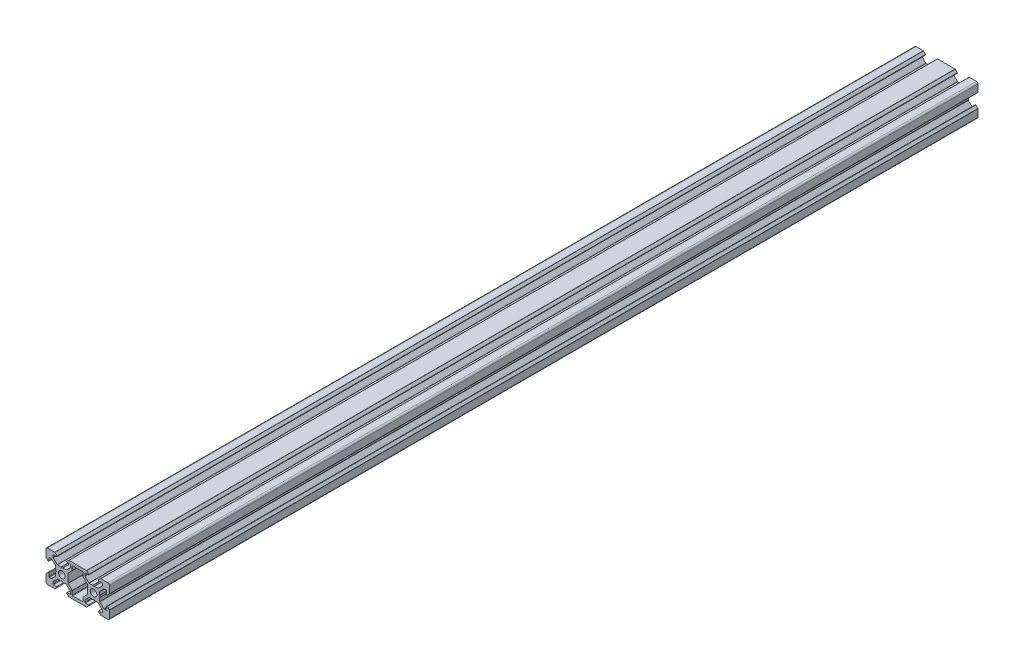
SolidWorks part; units mm, degrees
material "АД31Т ГОСТ 4784-97"
ref_plane "Спереди" through (0, 0, 0) normal (0, 0, 1) x (1, 0, 0)
ref_plane "Сверху" through (0, 0, 0) normal (0, 1, 0) x (1, 0, 0)
ref_plane "Справа" through (0, 0, 0) normal (1, 0, 0) x (0, 0, -1)
sketch "Эскиз1" plane through (0, 0, 0) normal (0, 0, 1) x (1, 0, 0)
  line L0 (12.9654, 0) -> (-12.9654, 0) construction
  line L1 (0, -12.9654) -> (0, 12.9654) construction
  line L2 (0, 0) -> (-18.3359, -18.3359) construction
  line L3 (-10, -10) -> (-10, -4.4)
  line L4 (-10, -4.4) -> (-8.2, -2.6)
  line L5 (-8.2, -2.6) -> (-8.2, -5.4993)
  line L6 (-8.2, -5.4993) -> (-6.56, -5.4993)
  line L7 (-6.56, -5.4993) -> (-3.9007, -2.84)
  line L8 (-3.9007, -2.84) -> (-3.9007, -0.5)
  line L9 (-3.9007, -0.5) -> (-3.4007, 0)
  line L10 (-0.5, -3.9007) -> (0, -3.4007)
  line L11 (-2.84, -3.9007) -> (-0.5, -3.9007)
  line L12 (-5.4993, -6.56) -> (-2.84, -3.9007)
  line L13 (-5.4993, -8.2) -> (-5.4993, -6.56)
  line L14 (-2.6, -8.2) -> (-5.4993, -8.2)
  line L15 (-4.4, -10) -> (-2.6, -8.2)
  line L16 (-10, -10) -> (-4.4, -10)
  line L17 (-10, 10) -> (-4.4, 10)
  line L18 (-4.4, 10) -> (-2.6, 8.2)
  line L19 (-2.6, 8.2) -> (-5.4993, 8.2)
  line L20 (-5.4993, 8.2) -> (-5.4993, 6.56)
  line L21 (-5.4993, 6.56) -> (-2.84, 3.9007)
  line L22 (-2.84, 3.9007) -> (-0.5, 3.9007)
  line L23 (-0.5, 3.9007) -> (0, 3.4007)
  line L24 (-3.9007, 0.5) -> (-3.4007, 0)
  line L25 (-3.9007, 2.84) -> (-3.9007, 0.5)
  line L26 (-6.56, 5.4993) -> (-3.9007, 2.84)
  line L27 (-8.2, 5.4993) -> (-6.56, 5.4993)
  line L28 (-8.2, 2.6) -> (-8.2, 5.4993)
  line L29 (-10, 4.4) -> (-8.2, 2.6)
  line L30 (-10, 10) -> (-10, 4.4)
  line L31 (0.5, 3.9007) -> (0, 3.4007)
  line L32 (0.5, -3.9007) -> (0, -3.4007)
  line L33 (10, -10) -> (10, 10) construction
  line L34 (3.9007, -0.5) -> (3.9007, 0.5)
  line L35 (6.56, -5.4993) -> (6.56, -8.2)
  line L36 (13.44, -5.4993) -> (16.0993, -2.84)
  line L37 (6.56, 5.4993) -> (3.9007, 2.84)
  line L38 (3.9007, 2.84) -> (3.9007, 0.5)
  line L39 (6.56, -8.2) -> (13.44, -8.2)
  line L40 (2.84, 3.9007) -> (0.5, 3.9007)
  line L41 (5.4993, 6.56) -> (2.84, 3.9007)
  line L42 (5.4993, 8.2) -> (5.4993, 6.56)
  line L43 (2.6, 8.2) -> (5.4993, 8.2)
  line L44 (4.4, 10) -> (2.6, 8.2)
  line L45 (15.6, 10) -> (4.4, 10)
  line L46 (15.6, -10) -> (4.4, -10)
  line L47 (4.4, -10) -> (2.6, -8.2)
  line L48 (2.6, -8.2) -> (5.4993, -8.2)
  line L49 (5.4993, -8.2) -> (5.4993, -6.56)
  line L50 (5.4993, -6.56) -> (2.84, -3.9007)
  line L51 (2.84, -3.9007) -> (0.5, -3.9007)
  line L52 (6.56, 5.4993) -> (6.56, 8.2)
  line L53 (3.9007, -2.84) -> (3.9007, -0.5)
  line L54 (6.56, -5.4993) -> (3.9007, -2.84)
  line L55 (16.0993, -2.84) -> (16.0993, -0.5)
  line L56 (6.56, 8.2) -> (13.44, 8.2)
  line L57 (13.44, 5.4993) -> (13.44, 8.2)
  line L58 (17.16, -3.9007) -> (19.5, -3.9007)
  line L59 (14.5007, -6.56) -> (17.16, -3.9007)
  line L60 (14.5007, -8.2) -> (14.5007, -6.56)
  line L61 (17.4, -8.2) -> (14.5007, -8.2)
  line L62 (15.6, -10) -> (17.4, -8.2)
  line L63 (15.6, 10) -> (17.4, 8.2)
  line L64 (17.4, 8.2) -> (14.5007, 8.2)
  line L65 (14.5007, 8.2) -> (14.5007, 6.56)
  line L66 (14.5007, 6.56) -> (17.16, 3.9007)
  line L67 (17.16, 3.9007) -> (19.5, 3.9007)
  line L68 (16.0993, 2.84) -> (16.0993, 0.5)
  line L69 (13.44, 5.4993) -> (16.0993, 2.84)
  line L70 (13.44, -5.4993) -> (13.44, -8.2)
  line L71 (16.0993, -0.5) -> (16.0993, 0.5)
  line L72 (19.5, -3.9007) -> (20, -3.4007)
  line L73 (19.5, 3.9007) -> (20, 3.4007)
  line L74 (30, 10) -> (30, 4.4)
  line L75 (30, 4.4) -> (28.2, 2.6)
  line L76 (28.2, 2.6) -> (28.2, 5.4993)
  line L77 (28.2, 5.4993) -> (26.56, 5.4993)
  line L78 (26.56, 5.4993) -> (23.9007, 2.84)
  line L79 (23.9007, 2.84) -> (23.9007, 0.5)
  line L80 (23.9007, 0.5) -> (23.4007, 0)
  line L81 (20.5, 3.9007) -> (20, 3.4007)
  line L82 (22.84, 3.9007) -> (20.5, 3.9007)
  line L83 (25.4993, 6.56) -> (22.84, 3.9007)
  line L84 (25.4993, 8.2) -> (25.4993, 6.56)
  line L85 (22.6, 8.2) -> (25.4993, 8.2)
  line L86 (24.4, 10) -> (22.6, 8.2)
  line L87 (30, 10) -> (24.4, 10)
  line L88 (30, -10) -> (24.4, -10)
  line L89 (24.4, -10) -> (22.6, -8.2)
  line L90 (22.6, -8.2) -> (25.4993, -8.2)
  line L91 (25.4993, -8.2) -> (25.4993, -6.56)
  line L92 (25.4993, -6.56) -> (22.84, -3.9007)
  line L93 (22.84, -3.9007) -> (20.5, -3.9007)
  line L94 (20.5, -3.9007) -> (20, -3.4007)
  line L95 (23.9007, -0.5) -> (23.4007, 0)
  line L96 (23.9007, -2.84) -> (23.9007, -0.5)
  line L97 (26.56, -5.4993) -> (23.9007, -2.84)
  line L98 (28.2, -5.4993) -> (26.56, -5.4993)
  line L99 (28.2, -2.6) -> (28.2, -5.4993)
  line L100 (30, -4.4) -> (28.2, -2.6)
  line L101 (30, -10) -> (30, -4.4)
  circle A0 centre (0, 0) radius 2.1
  circle A1 centre (20, 0) radius 2.1
  point P62 (10, 8.2)
  point P80 (10, -8.2)
  dimension "D5" = 2.6
  dimension "D10" = 4.2
  dimension "D2" = 10
  dimension "D3" = 1.64
  dimension "D4" = 1.5
  dimension "D6" = 1.8
  dimension "D7" = 2.84
  dimension "D8" = 0.5
  dimension "D9" = 45
extrude "Бобышка-Вытянуть1" add sketch "Эскиз1" along normal blind 548
fillet "Скругление1" radius 1 4 edges at (-10, 10, 274) (-10, -10, 274) (30, 10, 274) (30, -10, 274)
fillet "Скругление2" radius 0.3 83 edges at (-4.4, 10, 274) (-2.6, 8.2, 274) (-5.4993, 8.2, 274) (-5.4993, 6.56, 274) (-2.84, 3.9007, 274) (-0.5, 3.9007, 274) (0.5, 3.9007, 274) (2.84, 3.9007, 274) (5.4993, 6.56, 274) (4.4, 10, 274) (5.4993, 8.2, 274) (2.6, 8.2, 274) (3.9007, 2.84, 274) (3.9007, -2.84, 274) (4.4, -10, 274) (2.6, -8.2, 274) (5.4993, -8.2, 274) (5.4993, -6.56, 274) (2.84, -3.9007, 274) (0.5, -3.9007, 274) (-0.5, -3.9007, 274) (-2.84, -3.9007, 274) (-5.4993, -6.56, 274) (-5.4993, -8.2, 274) (-2.6, -8.2, 274) (-10, -4.4, 274) (-8.2, -2.6, 274) (-8.2, -5.4993, 274) (-6.56, -5.4993, 274) (-3.9007, -2.84, 274) (-3.9007, -0.5, 274) (-3.9007, 0.5, 274) (-3.9007, 2.84, 274) (-6.56, 5.4993, 274) (-8.2, 5.4993, 274) (-8.2, 2.6, 274) (-10, 4.4, 274) (6.56, -5.4993, 274) (6.56, 5.4993, 274) (6.56, 8.2, 274) (13.44, 8.2, 274) (13.44, 5.4993, 274) (16.0993, 2.84, 274) (16.0993, -2.84, 274) (13.44, -5.4993, 274) (13.44, -8.2, 274) (6.56, -8.2, 274) (15.6, 10, 274) (17.4, 8.2, 274) (14.5007, 8.2, 274) (14.5007, 6.56, 274) (17.16, 3.9007, 274) (19.5, 3.9007, 274) (20.5, 3.9007, 274) (22.84, 3.9007, 274) (25.4993, 6.56, 274) (25.4993, 8.2, 274) (22.6, 8.2, 274) (24.4, 10, 274) (30, 4.4, 274) (28.2, 2.6, 274) (28.2, 5.4993, 274) (26.56, 5.4993, 274) (23.9007, 2.84, 274) (23.9007, 0.5, 274) (23.9007, -0.5, 274) (23.9007, -2.84, 274) (26.56, -5.4993, 274) (28.2, -5.4993, 274) (28.2, -2.6, 274) (30, -4.4, 274) (24.4, -10, 274) (22.6, -8.2, 274) (25.4993, -8.2, 274) (25.4993, -6.56, 274) (22.84, -3.9007, 274) (20.5, -3.9007, 274) (19.5, -3.9007, 274) (17.16, -3.9007, 274) (14.5007, -6.56, 274) (14.5007, -8.2, 274) (17.4, -8.2, 274) (15.6, -10, 274)
